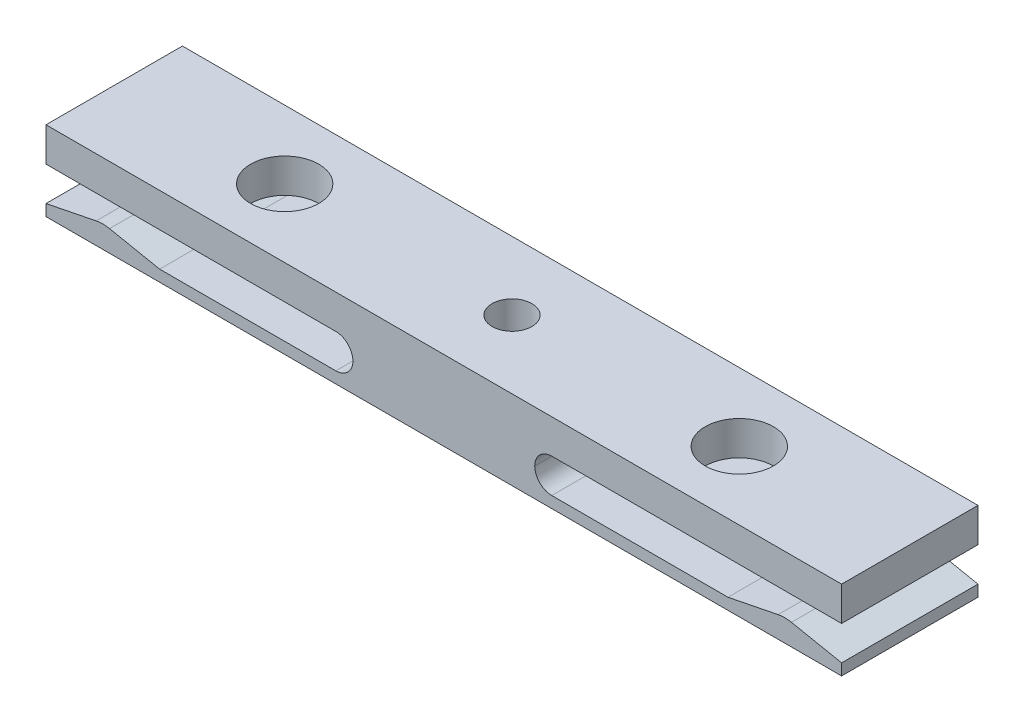
SolidWorks part; units mm, degrees
material "ABS-White"
ref_plane "Front Plane" through (0, 0, 0) normal (0, 0, 1) x (1, 0, 0)
ref_plane "Top Plane" through (0, 0, 0) normal (0, 1, 0) x (1, 0, 0)
ref_plane "Right Plane" through (0, 0, 0) normal (1, 0, 0) x (0, 0, -1)
sketch "Sketch1" plane through (0, 0, 0) normal (0, 0, 1) x (1, 0, 0)
  line L0 (0, 0) -> (3.9237, 0) construction
  line L1 (-35, 0) -> (-35, 1)
  line L2 (-35, 1) -> (-30, 2)
  line L3 (-30, 2) -> (-25, 1)
  line L4 (0, 1) -> (0, 0)
  line L5 (-25, 1) -> (0, 1)
  line L6 (-30, 2) -> (-30, 0) construction
  line L8 (0, 0) -> (-35, 0)
  dimension "D2" = 35
  dimension "D1" = 1
  dimension "D3" = 30
  dimension "D4" = 2
extrude "Boss-Extrude1" add sketch "Sketch1" along normal mid plane 12
sketch "Sketch5" plane through (0, 0, 0) normal (0, -1, 0) x (1, 0, 0)
  circle A0 centre (-20, 0) radius 4
  dimension "D1" = 8
  dimension "D2" = 20
extrude "Boss-Extrude2" add sketch "Sketch5" along normal blind 1
sketch "Sketch7" plane through (0, 0, 0) normal (0, 0, 1) x (1, 0, 0)
  line L0 (0, 1) -> (0, 7)
  line L1 (0, 7) -> (-35, 7)
  line L2 (-35, 7) -> (-35, 4)
  line L3 (-35, 4) -> (-8, 4)
  line L4 (-8, 4) -> (-8, 1)
  line L5 (0, 1) -> (-25, 1) construction
  line L6 (-8, 1) -> (0, 1)
  dimension "D2" = 8
  dimension "D3" = 2
  dimension "D4" = 3
extrude "Boss-Extrude3" add sketch "Sketch7" along normal mid plane 12
sketch "Sketch6" plane through (0, -1, 0) normal (0, -1, 0) x (1, 0, 0)
  circle A0 centre (-20, 0) radius 2
  dimension "D1" = 4
extrude "Cut-Extrude2" cut sketch "Sketch6" against normal through all
fillet "Fillet2" radius 3 1 edges at (-30, 2, 0)
fillet "Fillet3" radius 1.5 2 edges at (-8, 4, 0) (-8, 1, 0)
mirror "Mirror1" about plane through (0, 0, 0) normal (1, 0, 0) of bodies 105 101
sketch "Sketch3" plane through (0, 0, 0) normal (0, 1, 0) x (1, 0, 0)
  circle A0 centre (0, 0) radius 1.75
  dimension "D1" = 3.5
extrude "Cut-Extrude1" cut sketch "Sketch3" along normal through all
sketch "Sketch8" plane through (0, 7, 0) normal (0, 1, 0) x (1, 0, 0)
  circle A0 centre (20, 0) radius 3
  circle A1 centre (-20, 0) radius 3
  dimension "D1" = 6
extrude "Cut-Extrude3" cut sketch "Sketch8" against normal up to next
chamfer "Chamfer1" distance 1 angle 45 2 edges at (16, -1, 0) (-16, -1, 0)
